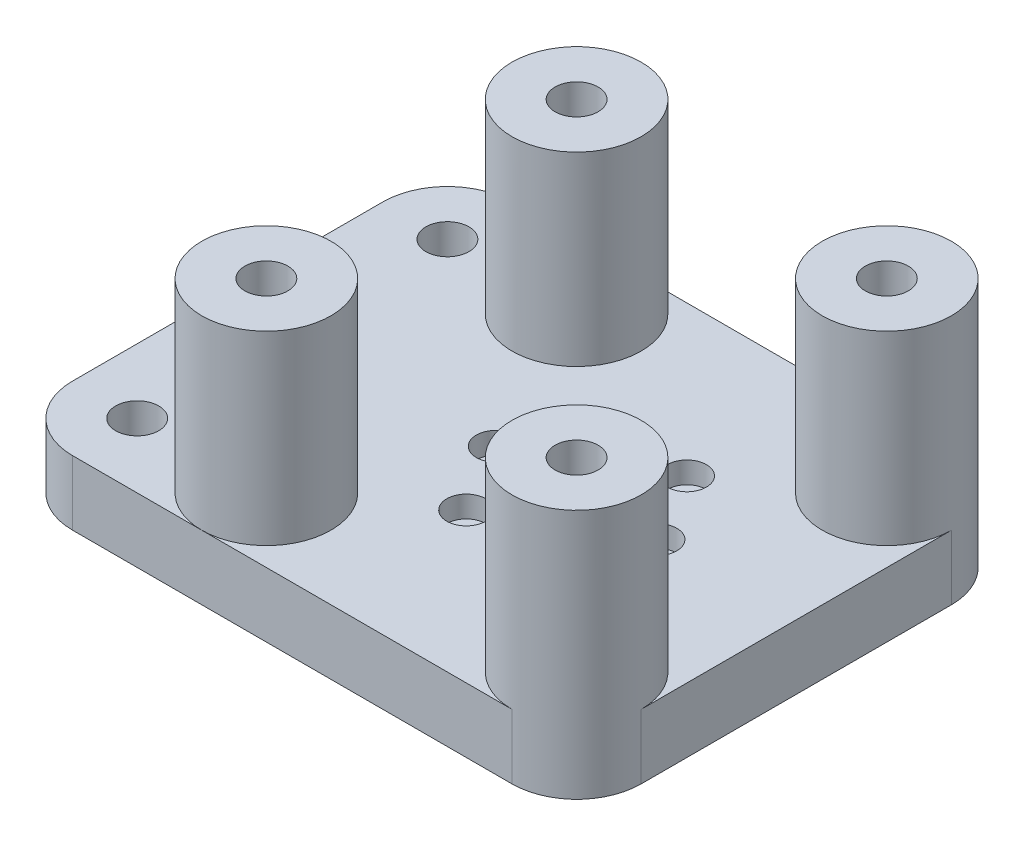
SolidWorks part; units mm, degrees
material "1060 Alloy"
ref_plane "Front" through (0, 0, 0) normal (0, 0, 1) x (1, 0, 0)
ref_plane "Top" through (0, 0, 0) normal (0, 1, 0) x (1, 0, 0)
ref_plane "Right" through (0, 0, 0) normal (1, 0, 0) x (0, 0, -1)
sketch "Sketch1" plane through (0, 0, 0) normal (0, 1, 0) x (1, 0, 0)
  line L0 (0, 0) -> (-28.8146, 28.8146) construction
  line L1 (-52.8146, 40.8146) -> (28.8146, 40.8146)
  line L2 (0, 0) -> (-7.5, 12.9904) construction
  line L3 (-52.8146, -40.8146) -> (28.8146, -40.8146)
  line L4 (-64.8146, 28.8146) -> (-64.8146, -28.8146)
  line L8 (40.8146, 28.8146) -> (40.8146, -28.8146)
  circle A0 centre (-28.8146, 28.8146) radius 4
  circle A1 centre (28.8146, 28.8146) radius 4
  circle A2 centre (28.8146, -28.8146) radius 4
  circle A3 centre (-28.8146, -28.8146) radius 4
  circle A4 centre (0, 0) radius 10.5
  circle A5 centre (-52.8146, 28.8146) radius 12 construction
  arc A6 (40.8146, 28.8146) -> (28.8146, 40.8146) centre (28.8146, 28.8146) ccw
  arc A7 (28.8146, -40.8146) -> (40.8146, -28.8146) centre (28.8146, -28.8146) ccw
  circle A8 centre (-28.8146, 28.8146) radius 12 construction
  circle A21 centre (0, 0) radius 15 construction
  circle A22 centre (-7.5, 12.9904) radius 2
  circle A23 centre (7.5, 12.9904) radius 2
  circle A24 centre (15, 0) radius 2
  circle A25 centre (7.5, -12.9904) radius 2
  circle A26 centre (-7.5, -12.9904) radius 2
  circle A27 centre (-15, 0) radius 2
  circle A30 centre (-52.8146, 28.8146) radius 4
  circle A31 centre (-52.8146, -28.8146) radius 4
  arc A32 (-64.8146, -28.8146) -> (-52.8146, -40.8146) centre (-52.8146, -28.8146) ccw
  arc A33 (-52.8146, 40.8146) -> (-64.8146, 28.8146) centre (-52.8146, 28.8146) ccw
  point P0 (0, 0)
  point P17 (0, 0)
  point P27 (0, 0)
  point P56 (0, 0)
  dimension "D5" = 8
  dimension "D6" = 21
  dimension "D9" = 30
  dimension "D11" = 4
  dimension "D8" = 12
  dimension "D3" = 40.75
  dimension "D2" = 12
  dimension "D7" = 12
  dimension "D4" = 4
  dimension "D12" = 6
extrude "base" add sketch "Sketch1" along normal blind 12
sketch "Sketch2" plane through (0, 12, 0) normal (0, 1, 0) x (1, 0, 0)
  circle A0 centre (0, 0) radius 15 construction
  circle A1 centre (-7.5, 12.9904) radius 3.625
  circle A2 centre (7.5, 12.9904) radius 3.625
  circle A3 centre (15, 0) radius 3.625
  circle A4 centre (7.5, -12.9904) radius 3.625
  circle A5 centre (-7.5, -12.9904) radius 3.625
  circle A7 centre (-15, 0) radius 3.625
  point P15 (0, 0)
  point P17 (0, 0)
  dimension "D1" = 7.25
  dimension "D2" = 6
extrude "bolt head recesses" cut sketch "Sketch2" against normal blind 4
sketch "Sketch3" plane through (0, 12, 0) normal (0, 1, 0) x (1, 0, 0)
  line L0 (28.8146, 40.8146) -> (-52.8146, 40.8146) construction
  line L1 (-52.8146, -40.8146) -> (28.8146, -40.8146) construction
  circle A0 centre (-28.8146, 28.8146) radius 12
  circle A1 centre (28.8146, 28.8146) radius 12
  circle A2 centre (28.8146, -28.8146) radius 12
  circle A3 centre (-28.8146, -28.8146) radius 12
  circle A4 centre (-28.8146, 28.8146) radius 4
  circle A5 centre (-28.8146, 28.8146) radius 4 construction
  circle A6 centre (28.8146, 28.8146) radius 4
  circle A7 centre (28.8146, -28.8146) radius 4
  circle A8 centre (-28.8146, -28.8146) radius 4
  point P14 (0, 0)
  point P26 (0, 0)
  dimension "D1" = 4
  dimension "D2" = 4
extrude "Boss-Extrude1" add sketch "Sketch3" along normal blind 34.5
equation "\"D3@Sketch1\"=\"square plate bolt pattern diameter\"/2"
equation "\"D1@base\" = \"motor mount plate thickness\""
equation "\"D5@Sketch1\" = \"square plate bolt bore\""
equation "\"D6@Sketch1\"=\"coupler OD\"+4mm"
equation "\"coupler motor shaft hole ID\"= 8mm"
equation "\"coupler OD\"= 17mm"
equation "\"coupler length\"= 25mm"
equation "\"square plate bolt pattern diameter\"= \"motor OD\" + \"square plate bolt head diameter\" + 4mm"
equation "\"motor mount m4 screw hole diameter\"= 4mm"
equation "\"motor mount m4 head diameter\"= 7.25mm"
equation "\"motor mount m4 head depth\"= 4mm"
equation "\"motor mount plate thickness\"= 8mm + \"motor mount m4 head depth\""
equation "\"motor shaft pride\"= 32mm"
equation "\"D7@Sketch1\"=\"motor mount post radius\""
equation "\"motor mount m4 pattern diamater\" = 30mm"
equation "\"D9@Sketch1\"=\"motor mount m4 pattern diamater\""
equation "\"D11@Sketch1\"=\"motor mount m4 screw hole diameter\""
equation "\"D1@Sketch2\"=\"motor mount m4 head diameter\""
equation "\"D1@bolt head recesses\" = \"motor mount m4 head depth\""
equation "\"motor OD\" = 64mm"
equation "\"square plate bolt bore\" = 8mm"
equation "\"square plate bolt head diameter\" = 13.5mm"
equation "\"motor to bearing plate distance\" = \"motor shaft pride\" + 2mm +\"coupler length\"/2"
equation "\"motor mount center bore\"= \"coupler OD\"+ 4mm"
equation "\"motor mount post radius\"= ( 3 * \"square plate bolt bore\" ) / 2"
equation "\"motor shaft diameter\"= 8mm"
equation "\"D2@Sketch1\"=\"motor mount post radius\""
equation "\"D8@Sketch1\"=\"motor mount post radius\""
equation "\"D1@Boss-Extrude1\"=\"motor to bearing plate distance\"-\"motor mount plate thickness\""
